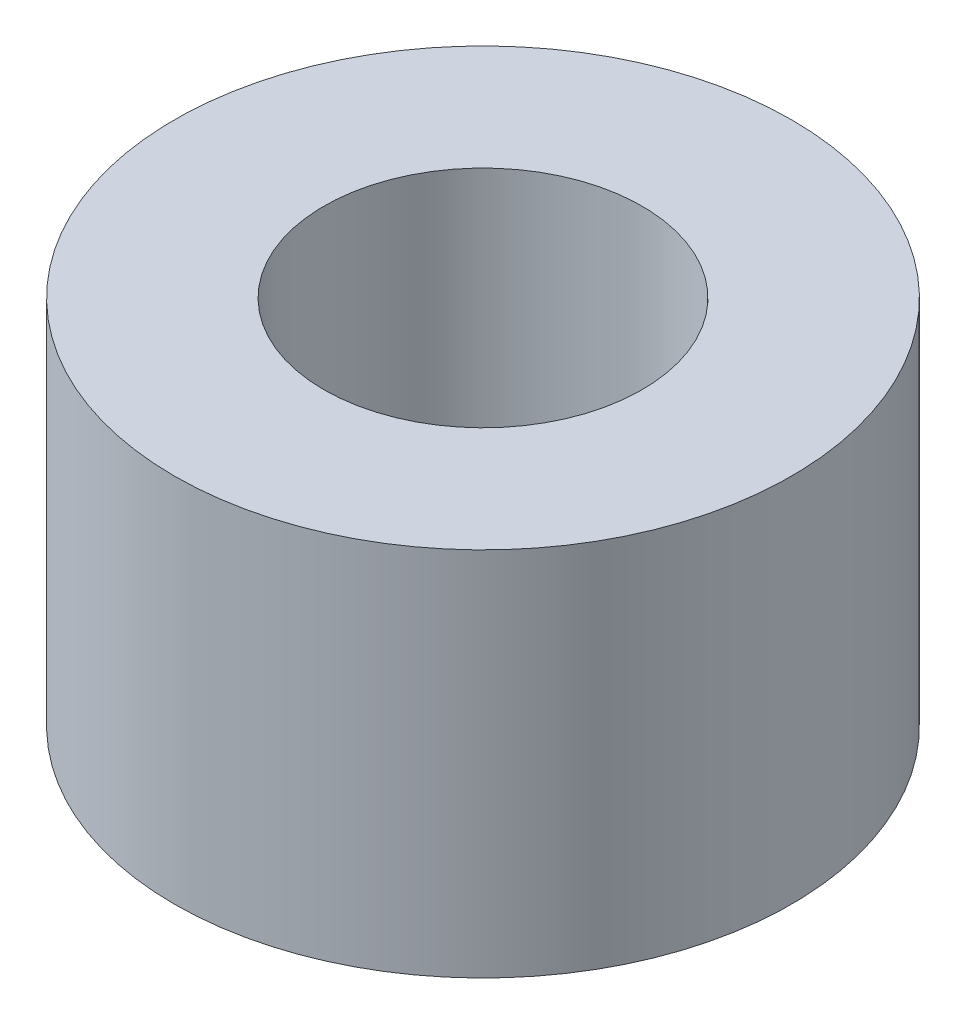
SolidWorks part; units mm, degrees
material "PET"
ref_plane "Front" through (0, 0, 0) normal (0, 0, 1) x (1, 0, 0)
ref_plane "Top" through (0, 0, 0) normal (0, 1, 0) x (1, 0, 0)
ref_plane "Right" through (0, 0, 0) normal (1, 0, 0) x (0, 0, -1)
sketch "Sketch1" plane through (0, 0, 0) normal (0, 1, 0) x (1, 0, 0)
  circle A0 centre (0, 0) radius 3.3782
  circle A1 centre (0, 0) radius 6.5532
  dimension "D1" = 6.7564
  dimension "D2" = 3.175
extrude "Boss-Extrude1" add sketch "Sketch1" along normal blind 7.874
